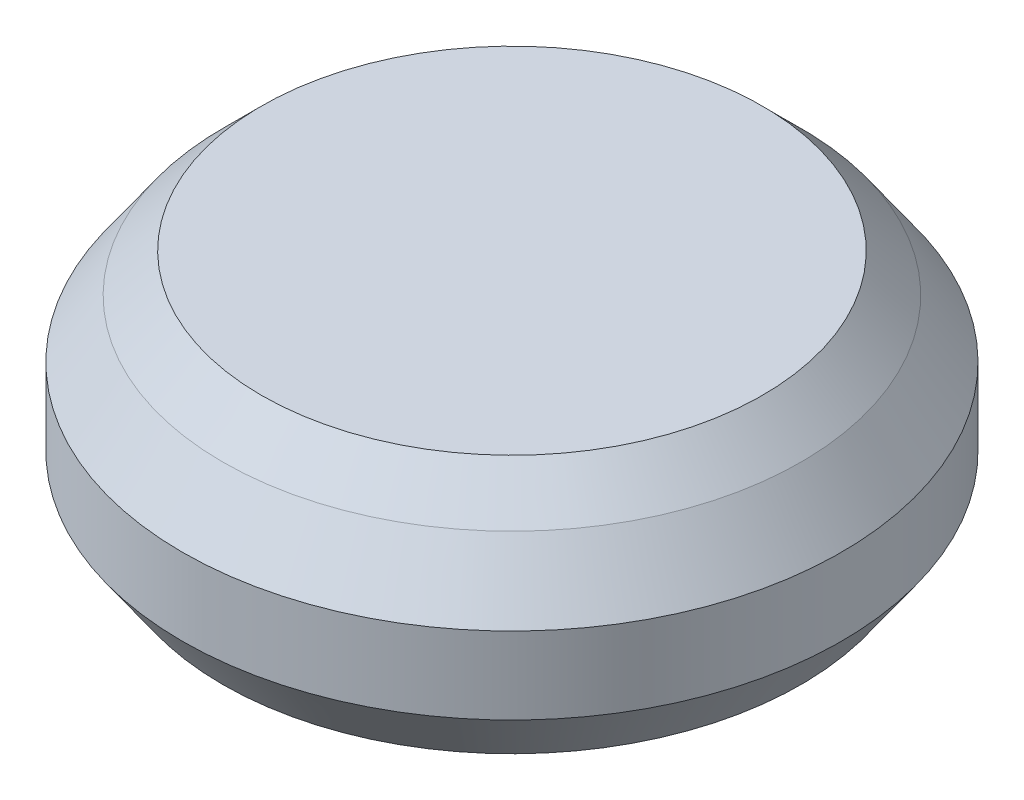
SolidWorks part; units mm, degrees
ref_plane "Alzado" through (0, 0, 0) normal (0, 0, 1) x (1, 0, 0)
ref_plane "Planta" through (0, 0, 0) normal (0, 1, 0) x (1, 0, 0)
ref_plane "Vista lateral" through (0, 0, 0) normal (1, 0, 0) x (0, 0, -1)
sketch "Croquis1" plane through (0, 0, 0) normal (0, 1, 0) x (1, 0, 0)
  circle A0 centre (0, 0) radius 15
  dimension "D1" = 30
extrude "Saliente-Extruir1" add sketch "Croquis1" along normal blind 3 draft 35 draft outward yes
sketch "Croquis2" plane through (0, 3, 0) normal (0, 1, 0) x (1, 0, 0)
  circle A0 centre (0, 0) radius 17.1006
  circle A1 centre (0, 0) radius 17.1006 construction
extrude "Saliente-Extruir2" add sketch "Croquis2" along normal blind 4
sketch "Croquis3" plane through (0, 7, 0) normal (0, 1, 0) x (1, 0, 0)
  circle A0 centre (0, 0) radius 17.1006
  circle A1 centre (0, 0) radius 17.1006 construction
extrude "Saliente-Extruir3" add sketch "Croquis3" along normal blind 3 draft 35
sketch "Croquis4" plane through (0, 10, 0) normal (0, 1, 0) x (1, 0, 0)
  circle A0 centre (0, 0) radius 15
  circle A1 centre (0, 0) radius 15 construction
extrude "Saliente-Extruir4" add sketch "Croquis4" along normal blind 2 draft 45 separate body
